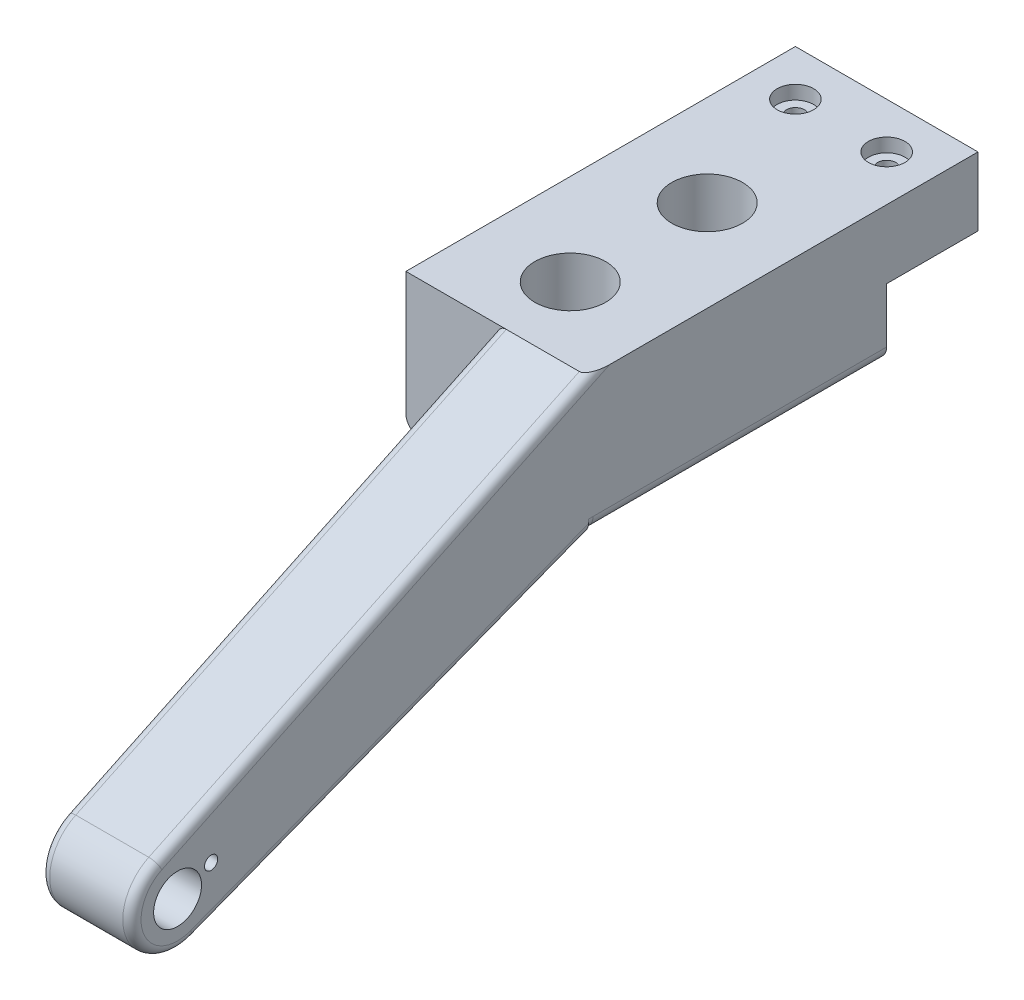
SolidWorks part; units mm, degrees
ref_plane "Front Plane" through (0, 0, 0) normal (0, 0, 1) x (1, 0, 0)
ref_plane "Top Plane" through (0, 0, 0) normal (0, 1, 0) x (1, 0, 0)
ref_plane "Right Plane" through (0, 0, 0) normal (1, 0, 0) x (0, 0, -1)
sketch "Sketch1" plane through (0, 0, 0) normal (0, 1, 0) x (1, 0, 0)
  line L1 (-20, 75) -> (20, 75)
  line L3 (-20, -75) -> (20, -75)
  line L4 (20, -75) -> (20, 75)
  line L5 (-20, -75) -> (-20, 75)
  circle A0 centre (0, -61.1649) radius 7.5
  circle A1 centre (0, -31.1649) radius 7.5
extrude "Boss-Extrude1" add sketch "Sketch1" against normal blind 30 contours L5 L1 L4 L3
sketch "Sketch3" plane through (0, 0, 0) normal (0, 1, 0) x (1, 0, 0)
  circle A0 centre (0, -60) radius 7.5
  circle A1 centre (0, -30) radius 7.5
extrude "Cut-Extrude1" cut sketch "Sketch3" against normal blind 30 contours A0 | A1
sketch "Sketch4" plane through (-20, 0, 0) normal (-1, 0, 0) x (0, 0, 1)
  line L1 (-75, -30) -> (-75, 0) construction
  line L2 (-75, -8) -> (0, -30)
  line L3 (75, -30) -> (-75, -30) construction
  line L4 (0, -30) -> (-75, -30)
  line L5 (-75, -30) -> (-75, -8)
extrude "Cut-Extrude2" cut sketch "Sketch4" against normal blind 49
sketch "Sketch6" plane through (0, 0, -75) normal (0, 0, -1) x (-1, 0, 0)
  line L1 (-20, 0) -> (20, 0)
  line L2 (-20, 0) -> (-20, -30)
  line L3 (-20, -30) -> (20, -30)
  line L4 (20, 0) -> (20, -30)
extrude "Boss-Extrude2" add sketch "Sketch6" along normal blind 50 and the other way blind 87
sketch "Sketch7" plane through (-20, 0, 0) normal (-1, 0, 0) x (0, 0, 1)
  line L1 (-125, -30) -> (-125, 0) construction
  line L2 (-125, -10) -> (-25, -30)
  line L3 (75, -30) -> (-125, -30) construction
  line L4 (-25, -30) -> (-125, -30)
  line L5 (-125, -30) -> (-125, -10)
extrude "Cut-Extrude3" cut sketch "Sketch7" against normal blind 50
sketch "Sketch8" plane through (0, 0, 75) normal (0, 0, 1) x (1, 0, 0)
  line L10 (20, -30) -> (6, -30)
  line L11 (-20, -30) -> (20, -30) construction
  line L12 (6, -30) -> (6, 0)
  line L13 (-20, 0) -> (20, 0) construction
  line L14 (6, 0) -> (20, 0)
  line L15 (20, 0) -> (20, -30)
  line L16 (-20, -30) -> (-6, -30)
  line L17 (-6, -30) -> (-6, 0)
  line L18 (-6, 0) -> (-20, 0)
  line L19 (-20, -30) -> (-20, 0) construction
  line L20 (-20, 0) -> (-20, -30)
extrude "Boss-Extrude4" add sketch "Sketch8" along normal blind 50
sketch "Sketch11" plane through (0, 0, 0) normal (0, 1, 0) x (1, 0, 0)
  line L0 (6, -75) -> (20, -75)
  line L1 (20, -125) -> (20, 125) construction
  line L2 (20, -75) -> (20, -125)
  line L3 (20, -125) -> (6, -125)
  line L4 (6, -125) -> (6, -75)
  line L5 (-6, -75) -> (-6, -125)
  line L6 (-6, -125) -> (-20, -125)
  line L7 (-20, -125) -> (-20, -75)
  line L8 (-20, -125) -> (-20, 125) construction
  line L9 (-20, -75) -> (-6, -75)
extrude "Cut-Extrude4" cut sketch "Sketch11" against normal blind 15
sketch "Sketch12" plane through (0, 0, 125) normal (0, 0, 1) x (1, 0, 0)
  line L1 (-20, -15) -> (-6, -15)
  line L2 (-20, -15) -> (-20, -30)
  line L3 (-20, -30) -> (-6, -30)
  line L4 (-6, -15) -> (-6, -30)
  line L5 (6, -15) -> (20, -15)
  line L6 (6, -15) -> (6, -30)
  line L7 (6, -30) -> (20, -30)
  line L8 (20, -15) -> (20, -30)
extrude "Boss-Extrude5" add sketch "Sketch12" along normal blind 10
sketch "Sketch13" plane through (-6, 0, 0) normal (1, 0, 0) x (0, 0, -1)
  circle A0 centre (-125, -22.5) radius 5
extrude "Boss-Extrude6" add sketch "Sketch13" along normal up to surface (12 mm away) contours A0 up to face at (6, -22.5, 105)
sketch "Sketch14" plane through (0, -30, 0) normal (0, -1, 0) x (1, 0, 0)
  circle A0 centre (0, 60) radius 7.5
  circle A1 centre (0, 60) radius 6
  circle A2 centre (0, 30) radius 6
  circle A3 centre (0, 30) radius 7.5
extrude "Boss-Extrude7" add sketch "Sketch14" against normal blind 5
sketch "Sketch15" plane through (20, 0, 0) normal (1, 0, 0) x (0, 0, -1)
  line L0 (125, 0) -> (105, 0)
  line L1 (-75, 0) -> (125, 0) construction
  circle A0 centre (52.5, 373.9316) radius 377.5991
extrude "Cut-Extrude5" cut sketch "Sketch15" against normal blind 50 contours A0
fillet "Fillet1" radius 3 2 edges at (20, -30, 55) (-20, -30, 55)
fillet "Fillet2" radius 3 8 edges at (-20, -18.5, -82.5) (-19.1213, -29.1213, -29.3934) (0, -30, -25) (19.1213, -29.1213, -29.3934) (-20, -5, -125) (20, -5, -125) (0, -10, -125) (20, -18.5, -82.5)
sketch "Sketch17" plane through (0, 0, 75) normal (0, 0, 1) x (1, 0, 0)
  line L0 (20, 0) -> (20, -30)
  line L1 (14.0365, -30) -> (20, -30)
  line L2 (6, -30) -> (17, -30) construction
  line L3 (20, 0) -> (-20, 0)
  line L4 (-20, 0) -> (-20, -30)
  line L5 (-20, -30) -> (14.0365, -30)
extrude "Boss-Extrude11" add sketch "Sketch17" along normal up to surface (60 mm away) up to face at (13.9243, -23.5243, 135)
sketch "Sketch23" plane through (0, 0, 135) normal (0, 0, 1) x (1, 0, 0)
  line L0 (-20, -15) -> (0, -15)
  line L1 (-20, 0) -> (-20, -30) construction
  line L3 (0, -30) -> (0, -15)
  line L4 (-20, -30) -> (20, -30) construction
  line L6 (-20, -30) -> (0, -30)
  line L7 (-20, -15) -> (-20, -30)
  line L9 (-20, -30) -> (20, -30)
  line L10 (-20, -30) -> (-20, 0)
  line L11 (-20, 0) -> (20, 0)
  line L12 (20, -30) -> (20, 0)
  line M1 (-20, 0) -> (-20, -30)
  line M2 (-20, -30) -> (20, -30)
  line M3 (20, -30) -> (20, 0)
  line M4 (20, 0) -> (-20, 0)
extrude "Cut-Extrude8" cut sketch "Sketch23" against normal up to surface (60 mm away) contours L3 L0 M2 M3 M4 M1 region at (3.3333, -12.5, 135) up to face at (19.2071, -29.2071, 75)
sketch "Sketch25" plane through (0, 0, 75) normal (0, 0, 1) x (1, 0, 0)
  line L0 (-20, -15) -> (-20, 0)
  line L1 (-20, 0) -> (0, 0)
  line L2 (-20, 0) -> (20, 0) construction
  line L3 (0, 0) -> (0, -15)
  line L4 (0, -15) -> (-20, -15)
extrude "Boss-Extrude13" add sketch "Sketch25" along normal up to surface (60 mm away) up to face at (-10, -22.5, 135)
sketch "Sketch26" plane through (0, 0, 0) normal (1, 0, 0) x (0, 0, -1)
  circle A0 centre (-125, -15) radius 5
extrude "Boss-Extrude14" add sketch "Sketch26" along normal up to surface (20 mm away) up to face at (20, -9.3154, -31.9576)
sketch "Sketch27" plane through (0, 0, 75) normal (0, 0, 1) x (1, 0, 0)
  line L1 (20, 0) -> (-20, 0)
  line L2 (20, 0) -> (20, -60)
  line L3 (20, -60) -> (-20, -60)
  line L4 (-20, 0) -> (-20, -60)
extrude "Boss-Extrude15" add sketch "Sketch27" along normal up to surface (60 mm away) up to face at (-10, -15, 135)
sketch "Sketch28" plane through (0, 0, 75) normal (0, 0, -1) x (-1, 0, 0)
  line L0 (20, -27) -> (20, -60) construction
  line L1 (-20, -60) -> (20, -60)
  line L2 (-20, -60) -> (-20, -30)
  line L3 (-20, -30) -> (20, -30)
  line L4 (20, -60) -> (20, -30)
extrude "Cut-Extrude9" cut sketch "Sketch28" against normal blind 1
sketch "Sketch29" plane through (0, 0, 135) normal (0, 0, 1) x (1, 0, 0)
  line L0 (20, 0) -> (-20, 0) construction
  line L1 (20, -60) -> (0, -60)
  line L2 (20, -60) -> (20, 0)
  line L3 (20, 0) -> (0, 0)
  line L4 (0, -60) -> (0, 0)
extrude "Cut-Extrude10" cut sketch "Sketch29" against normal up to surface (59 mm away) up to face at (0, -45, 76)
fillet "Fillet6" radius 3 1 edges at (-20, -30, 75.5)
fillet "Fillet7" radius 3 1 edges at (20, -30, 75.5)
sketch "Sketch30" plane through (0, 0, 135) normal (0, 0, 1) x (1, 0, 0)
  line L0 (-20, 0) -> (-20, -30)
  line L1 (-20, 0) -> (-20, -60) construction
  line L2 (-20, -15) -> (0, -15)
  line L3 (0, 0) -> (0, -60) construction
  line L4 (0, -15) -> (0, 0)
  line L5 (0, 0) -> (-20, 0)
  line M1 (0, -60) -> (0, 0)
  line M2 (0, 0) -> (-20, 0)
  line M3 (-20, 0) -> (-20, -60)
extrude "Cut-Extrude11" cut sketch "Sketch30" against normal up to surface (59 mm away) contours L2 M3 M1 M2 region at (-10, -7.5, 135) up to face at (11.5243, -17.5243, 76)
sketch "Sketch31" plane through (0, 0, 0) normal (1, 0, 0) x (0, 0, -1)
  line L0 (-129.7694, -41.2162) -> (-129.0122, -40.847)
  line L1 (-76, -15) -> (-76, -30)
  line L2 (-76, -30) -> (-118.7075, -57.7744)
  line L3 (-129.6113, -41.0081) -> (-129.7694, -41.2162)
  line L4 (-89.6197, -15) -> (-129.6113, -41.0081)
  line L5 (-76, -30) -> (-76, -60)
  line L6 (-76, -60) -> (-135, -60)
  line L7 (-135, -60) -> (-135, -15)
  line L8 (-135, -15) -> (-76, -15)
  line L9 (-96, -19.1494) -> (-129.6113, -41.0081) construction
  line L10 (-96, -15) -> (-96, -19.1494) construction
  circle A0 centre (-125.0122, -50.0122) radius 10
  line M9 (-76, -15) -> (-135, -15)
  line M10 (-135, -15) -> (-135, -60)
  line M11 (-135, -60) -> (-76, -60)
  line M12 (-76, -60) -> (-76, -30)
  dimension "D1" = 20
extrude "Cut-Extrude13" cut sketch "Sketch31" against normal blind 28 contours A0 M10 M11 | A0 L2 M11 M12 | A0 L3 L4 M9 M10 region at (0, -24.9817, 119.9741) region at (0, -57.7806, 132.7806) region at (0, -50.0084, 91.4032)
sketch "Sketch32" plane through (0, 0, 0) normal (1, 0, 0) x (0, 0, -1)
  line L0 (-76, -30) -> (-76, 0)
  line L1 (-76, 0) -> (-129.7694, -41.2162)
  line L2 (-129.7694, -41.2162) -> (-76, -30)
extrude "Boss-Extrude16" add sketch "Sketch32" against normal up to surface (20 mm away) up to face at (-20, -28.5466, 55.3206)
sketch "Sketch33" plane through (0, 0, 0) normal (1, 0, 0) x (0, 0, -1)
  circle A0 centre (-125.0122, -50.0122) radius 5
extrude "Boss-Extrude17" add sketch "Sketch33" along normal up to surface (20 mm away) contours A0 up to face at (20, -11.526, -18.3379)
ref_plane "Plane2" through (0, 10, 0) normal (0, 1, 0) x (1, 0, 0)
sketch "Sketch34" plane through (0, 0, 0) normal (1, 0, 0) x (0, 0, -1)
  line L0 (-129.6113, -41.0081) -> (-129.7694, -41.2162)
  line L1 (-129.6113, -41.0081) -> (-76, 0)
  line L2 (-76, 0) -> (-76, -30)
  line L3 (-76, -30) -> (-76, 0) construction
  line L4 (-76, -30) -> (-118.7075, -57.7744)
  arc A0 (-129.7694, -41.2162) -> (-118.7075, -57.7744) centre (-125.0122, -50.0122) ccw
extrude "Cut-Extrude15" cut sketch "Sketch34" against normal up to surface (20 mm away) up to face at (-20, -30.8448, 56.4126)
extrude "Cut-Extrude16" cut sketch "Sketch34<2>" along normal up to surface (20 mm away) up to face at (20, -11.526, -18.3379)
sketch "Sketch34<2>" plane through (0, 0, 0) normal (1, 0, 0) x (0, 0, -1) same geometry as "Sketch34"
extrude "Boss-Extrude19" add sketch "Sketch34<3>" along normal up to surface (20 mm away) up to face at (20, -11.526, -18.3379)
sketch "Sketch34<3>" plane through (0, 0, 0) normal (1, 0, 0) x (0, 0, -1) same geometry as "Sketch34"
sketch "Sketch38" plane through (0, 0, 0) normal (-1, 0, 0) x (0, 0, 1)
  circle A0 centre (125.0122, -50.0122) radius 5
sketch "Sketch39" plane through (0, 0, 0) normal (-1, 0, 0) x (0, 0, 1)
  line L0 (162.0273, -59.1835) -> (76, -78.9424)
  line L1 (169.997, -40.8408) -> (76, 0)
  line L2 (76, -30) -> (76, 0) construction
  line L3 (76, 0) -> (129.6113, -41.0081) construction
  line L4 (76, 0) -> (76, -30)
  line L6 (162.0273, -59.1835) -> (76, -30)
  line L7 (76, -78.9424) -> (76, -30)
  arc A0 (162.0273, -59.1835) -> (169.997, -40.8408) centre (166.0122, -50.0122) ccw
  line M6 (129.6113, -41.0081) -> (76, 0)
  line M8 (76, -30) -> (118.7075, -57.7744)
  arc M9 (118.7075, -57.7744) -> (129.7694, -41.2162) centre (125.0122, -50.0122) ccw
  line M10 (129.7694, -41.2162) -> (129.6113, -41.0081)
extrude "Cut-Extrude17" cut sketch "Sketch39" against normal blind 23 contours L7 L0 L6 M9 M8 | L6 M9 M8 region at (0, -58.461, 102.3812) region at (0, -47.5284, 112.7515)
extrude "Boss-Extrude21" add sketch "Sketch39<3>" against normal blind 20 contours L6 A0 L1 M6 M10 M9 region at (0, -36.3816, 138.4753)
sketch "Sketch39<3>" plane through (0, 0, 0) normal (-1, 0, 0) x (0, 0, 1) same geometry as "Sketch39"
sketch "Sketch40" plane through (0, -4.0074, 0) normal (-1, 0, 0) x (0, 0, 1)
  circle A0 centre (166.0122, -50.0122) radius 4.5
extrude "Boss-Extrude22" add sketch "Sketch40" along normal up to surface (12 mm away)
ref_plane "Plane5" through (0, 0, 0) normal (-1, 0, 0) x (0, 0, 1)
sketch "Sketch42" plane through (0, 0, 0) normal (-1, 0, 0) x (0, 0, 1)
  line L0 (166.0122, -54.0196) -> (166.0122, -54.0122)
  line L1 (170.3172, -44.9863) -> (76, 0)
  line L2 (76, 0) -> (76, -30)
  line L3 (162.4124, -63.3418) -> (76, -30)
  line L4 (175.8593, -55.7544) -> (179.2704, -36.4741)
  line L5 (179.2704, -36.4741) -> (76, 0)
  circle A0 centre (166.0122, -54.0122) radius 10
extrude "Cut-Extrude18" cut sketch "Sketch42" against normal blind 20 contours A0 L4 L5 L1 region at (0, -28.5967, 144.6768)
extrude "Boss-Extrude23" add sketch "Sketch42<4>" against normal blind 20 contours A0 L1 L2 L3 | A0 region at (0, -31.8969, 115.5317) region at (0, -48.8269, 174.2302)
sketch "Sketch42<4>" plane through (0, 0, 0) normal (-1, 0, 0) x (0, 0, 1) same geometry as "Sketch42"
fillet "Fillet8" radius 2 6 edges at (20, -46.6709, 119.2062) (20, -57.9675, 175.1967) (0, -46.6709, 119.2062) (0, -57.9675, 175.1967) (20, -22.4932, 123.1586) (0, -22.4932, 123.1586)
sketch "Sketch44" plane through (20, 0, 0) normal (1, 0, 0) x (0, 0, -1)
  line L0 (0, 0) -> (105, 0)
  line L1 (105, 0) -> (105, -4.5055)
  line L2 (105, -4.5055) -> (0, -4.5055)
  line L3 (0, -4.5055) -> (0, 0)
extrude "Boss-Extrude25" add sketch "Sketch44" against normal up to surface (40 mm away) up to face at (-20, -11.526, -18.3379)
sketch "Sketch46" plane through (20, 0, 0) normal (1, 0, 0) x (0, 0, -1)
  line L0 (-71.3543, 0) -> (122, 0) construction
  line L1 (25.3229, 0) -> (-14.6771, 0)
  line L2 (25.3229, 0) -> (25.3229, -6)
  line L3 (25.3229, -27) -> (-14.6771, -27)
  line L4 (-14.6771, 0) -> (-14.6771, -27)
  line L5 (-75, -27) -> (24.7029, -27) construction
  line L6 (63.8734, -19.1659) -> (62.5127, -12.362)
  line L7 (24.7029, -27) -> (122, -7.5406) construction
  line L8 (19.3229, -6) -> (-8.6771, -6)
  line L9 (-8.6771, -6) -> (-8.6771, -21)
  line L10 (19.3229, -21) -> (-8.6771, -21)
  line L12 (19.3229, -21) -> (94.3229, -6)
  line L13 (19.3229, -6) -> (103.4664, -6)
  line L14 (25.3229, -19.8) -> (25.3229, -27)
  line L15 (19.3229, -6) -> (19.3229, -21) construction
  line L16 (25.3229, 0) -> (25.3229, -27) construction
  dimension "D1" = 6
extrude "Cut-Extrude20" cut sketch "Sketch46" against normal blind 59 and the other way through all contours L13 L8 L9 L10 L12 region at (20, -12.0687, -27.6511)
fillet "Fillet10" radius 2 1 edges at (0, -6, -94.3229)
sketch "Sketch48" plane through (0, 0, 8.6771) normal (0, 0, -1) x (-1, 0, 0)
  line L0 (-20, -21) -> (20, -21)
  line L1 (-20, -21) -> (-20, -6)
  line L2 (20, -21) -> (20, -6)
  line L3 (-20, -6) -> (20, -6)
extrude "Boss-Extrude28" add sketch "Sketch48" along normal blind 28
sketch "Sketch49" plane through (20, 0, 0) normal (1, 0, 0) x (0, 0, -1)
  line L0 (19.3229, -6) -> (19.3229, 0)
  line L7 (-71.3543, 0) -> (122, 0) construction
  line L8 (19.3229, -6) -> (19.3229, -30)
  line L9 (19.3229, -30) -> (-20.6771, -30)
  line L10 (-20.6771, -30) -> (-20.6771, 0)
  line L11 (-20.6771, 0) -> (19.3229, 0)
  line L12 (-20.6771, -30) -> (-10.6771, -30)
  line L13 (-10.6771, -30) -> (-10.6771, -15)
  line L14 (-10.6771, -15) -> (9.3229, -15)
  line L15 (9.3229, -15) -> (9.3229, 0)
  line M5 (19.3229, -21) -> (19.3229, -6)
  line M9 (122, 0) -> (-71.3543, 0)
  line M15 (-75, -27) -> (24.7029, -27)
sketch "Sketch50" plane through (0, 0, 0) normal (0, 1, 0) x (1, 0, 0)
  line L0 (20, 9.3229) -> (-20, 9.3229)
  line L1 (-20, -76) -> (-20, 122) construction
  line L2 (-20, 9.3229) -> (-20, -0.6771)
  line L3 (-20, -0.6771) -> (-10, -0.6771)
  line L4 (-10, -0.6771) -> (10, -0.6771)
  circle A0 centre (10, -0.6771) radius 2
  circle A1 centre (-10, -0.6771) radius 2
extrude "Cut-Extrude21" cut sketch "Sketch49" against normal blind 49 contours L15 L14 L13 L8 L0 M15 M5 M9 | L13 L9 L8 M15 region at (20, -17.0294, -7.264) region at (20, -28.5, -4.3229)
sketch "Sketch51" plane through (0, 0, -19.3229) normal (0, 0, 1) x (1, 0, 0)
  line L1 (24.2973, -37.591) -> (-28.6622, -37.591)
  line L2 (24.2973, -37.591) -> (24.2973, 2.6321)
  line L3 (24.2973, 2.6321) -> (-28.6622, 2.6321)
  line L4 (-28.6622, -37.591) -> (-28.6622, 2.6321)
extrude "Cut-Extrude22" cut sketch "Sketch51" against normal blind 136
extrude "Cut-Extrude23" cut sketch "Sketch50" against normal blind 136 contours A0 | L3 A1 L4 | L4 A1 L3 region at (-10, 0, -0.1717) region at (10, 0, -1.2663) region at (-10, 0, 1.526)
sketch "Sketch52" plane through (0, 0, 0) normal (0, 1, 0) x (1, 0, 0)
  circle A0 centre (10, -0.6771) radius 4
  circle A1 centre (-10, -0.6771) radius 4
  circle A2 centre (10, -0.6771) radius 1.5
  circle A3 centre (-10, -0.6771) radius 1.5
extrude "Cut-Extrude24" cut sketch "Sketch52" against normal blind 3
sketch "Sketch54" plane through (0, 0, 0) normal (0, 1, 0) x (1, 0, 0)
  circle A0 centre (0, -60) radius 7.75
  circle A1 centre (0, -30) radius 7.75
extrude "Cut-Extrude26" cut sketch "Sketch54" against normal up to surface (25 mm away) up to face at (0, -25, 54)
sketch "Sketch55" plane through (20, 0, 0) normal (1, 0, 0) x (0, 0, -1)
  circle A0 centre (-166.0122, -54.0122) radius 5.25
  circle A2 centre (-158.6646, -50.8479) radius 1.5
extrude "Cut-Extrude27" cut sketch "Sketch55" against normal blind 35 contours A0
sketch "Sketch56" plane through (20, 0, 0) normal (1, 0, 0) x (0, 0, -1)
  circle A1 centre (-158.6646, -50.8479) radius 1.45
extrude "Cut-Extrude28" cut sketch "Sketch56" against normal blind 22
sketch "Sketch58" plane through (0, 0, 0) normal (-1, 0, 0) x (0, 0, 1)
  circle A0 centre (166.0122, -54.0122) radius 5.25
  circle A1 centre (166.0122, -54.0122) radius 7.25
